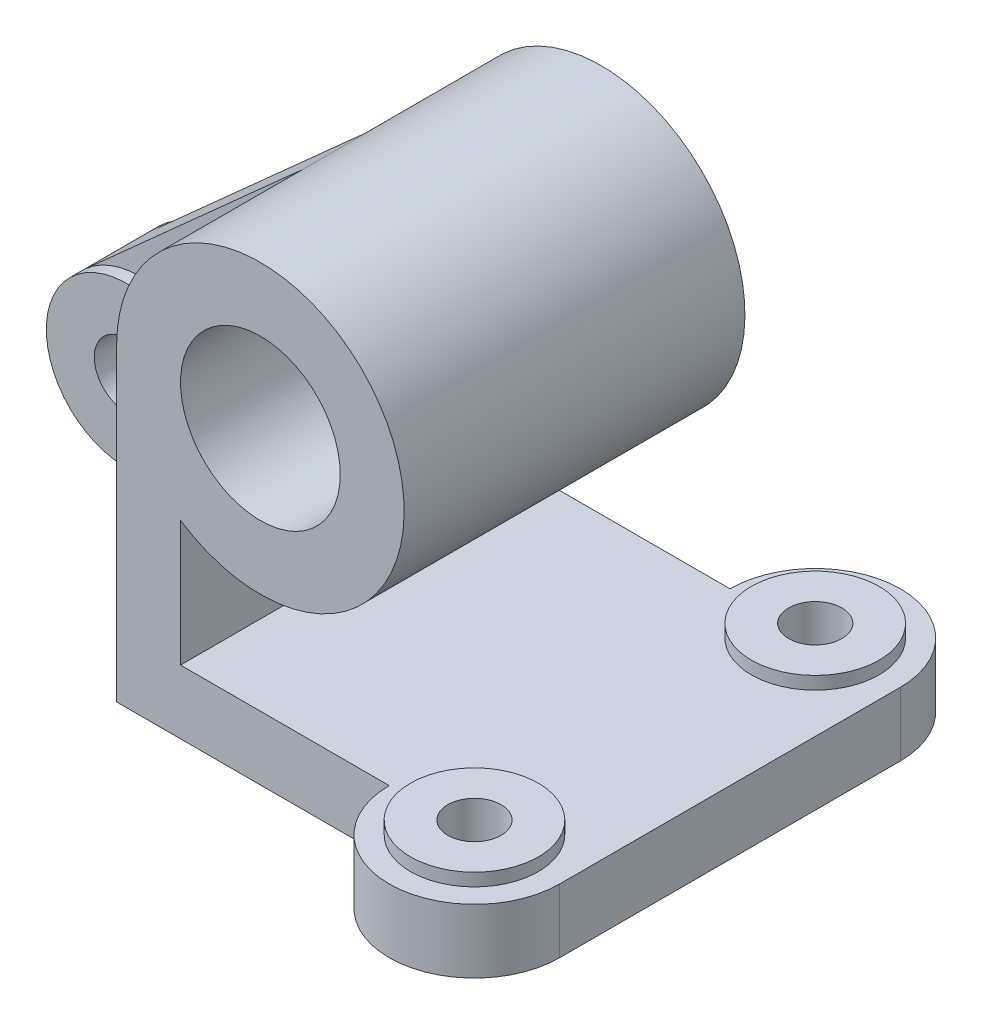
SolidWorks part; units mm, degrees
ref_plane "Front Plane" through (0, 0, 0) normal (0, 0, 1) x (1, 0, 0)
ref_plane "Top Plane" through (0, 0, 0) normal (0, 1, 0) x (1, 0, 0)
ref_plane "Right Plane" through (0, 0, 0) normal (1, 0, 0) x (0, 0, -1)
sketch "Sketch1" plane through (0, 0, 0) normal (0, 0, 1) x (1, 0, 0)
  line L0 (-67.5, 0) -> (-67.5, -144.9987)
  line L1 (-67.5, -144.9987) -> (100.5, -144.9987)
  line L2 (100.5, -144.9987) -> (100.5, -114.9987)
  line L3 (100.5, -114.9987) -> (-37.5, -114.9987)
  line L4 (-37.5, -114.9987) -> (-37.5, -56.1249)
  line L5 (-141.1545, -101.2377) -> (-67.5, -144.9987)
  line L6 (-147.0194, -41.0652) -> (-45.035, 50.2802)
  line L7 (20.5, -114.9987) -> (20.5, -144.9987)
  circle A0 centre (0, 0) radius 67.5
  circle A1 centre (0, 0) radius 37.5
  circle A2 centre (-122, -68.9987) radius 15
  circle A3 centre (-122, -68.9987) radius 37.5
  dimension "D2" = 135
  dimension "D3" = 75
  dimension "D5" = 30
  dimension "D6" = 75
  dimension "D1" = 30
  dimension "D4" = 30
  dimension "D7" = 76
  dimension "D8" = 80
  dimension "D9" = 168
  dimension "D10" = 122
extrude "Boss-Extrude3" add sketch "Sketch1" along normal mid plane 160 contours A0 L0 L1 L7 L3 L4 | A0 A1 | L3 L7 L1 L2 region at (-37.5545, -105.1206, 0) region at (-59.8853, 26.7565, 0) region at (60.5, -129.9987, 0)
extrude "Boss-Extrude4" add sketch "Sketch1<5>" along normal mid plane 30 contours A3 L5 L0 A0 L6 region at (-86.6519, -55.5421, 0)
sketch "Sketch1<5>" plane through (0, 0, 0) normal (0, 0, 1) x (1, 0, 0) same geometry as "Sketch1"
extrude "Boss-Extrude5" add sketch "Sketch1<6>" along normal mid plane 42 contours A3 A2 region at (-158.2675, -72.5336, 0)
sketch "Sketch1<6>" plane through (0, 0, 0) normal (0, 0, 1) x (1, 0, 0) same geometry as "Sketch1"
sketch "Sketch3" plane through (0, -114.9987, 0) normal (0, 1, 0) x (1, 0, 0)
  line L0 (100.5, 0) -> (146.9667, 0) construction
  line L1 (100.5, -80) -> (100.5, 80) construction
  line L2 (140.5, 80) -> (140.5, -80)
  line L3 (100.5, 80) -> (100.5, -80)
  line L4 (100.5, 80) -> (140.5, 80)
  arc A0 (100.5, -40) -> (140.5, -80) centre (100.5, -80) ccw
  circle A1 centre (100.5, -80) radius 30
  circle A2 centre (100.5, -80) radius 12.5
  arc A3 (100.5, 40) -> (140.5, 80) centre (100.5, 80) cw
  circle A4 centre (100.5, 80) radius 30
  circle A5 centre (100.5, 80) radius 12.5
  line M3 (100.5, 80) -> (-37.5, 80)
  line M5 (-37.5, -80) -> (100.5, -80)
  line M6 (100.5, -80) -> (100.5, 80)
  dimension "D1" = 80
  dimension "D2" = 60
  dimension "D3" = 25
extrude "Boss-Extrude13" add sketch "Sketch3" along normal blind 30 from surface contours L0 L2 L4 A4 M6 | L0 L3 A1 A0 L2 M5 | A4 L4 A3 M3 region at (122.5605, -114.9987, -32.2691) region at (115.8088, -114.9987, 53.743) region at (135.5, -114.9987, -80.8944) starting at face at (-11.5, -144.9987, 0)
extrude "Boss-Extrude14" add sketch "Sketch3<10>" along normal blind 36 from surface contours A2 A1 L3 M5 | A2 L3 A1 M5 | A5 L4 A4 M3 | L4 A5 L3 A4 | L3 A5 A4 M3 region at (114.7927, -114.9987, -65.7073) region at (100.5, -114.9987, -94.2927) region at (86.2073, -114.9987, -65.7073) region at (79.25, -114.9987, 80.8485) region at (86.2073, -114.9987, 65.7073) starting at face at (102.5711, -144.9987, -82.0711)
sketch "Sketch3<10>" plane through (0, -114.9987, 0) normal (0, 1, 0) x (1, 0, 0) same geometry as "Sketch3"
extrude "Cut-Extrude3" cut sketch "Sketch3<11>" against normal through all contours A2 M6 M5 | A2 M5 M6 | A5 L4 M3 | A5 L4 M6 | A5 M6 M3 region at (105.8052, -114.9987, -74.6948) region at (100.5, -114.9987, -85.3052) region at (95.1948, -114.9987, -74.6948) region at (102.2684, -114.9987, 81.7684) region at (95.1948, -114.9987, 74.6948)
sketch "Sketch3<11>" plane through (0, -114.9987, 0) normal (0, 1, 0) x (1, 0, 0) same geometry as "Sketch3"
